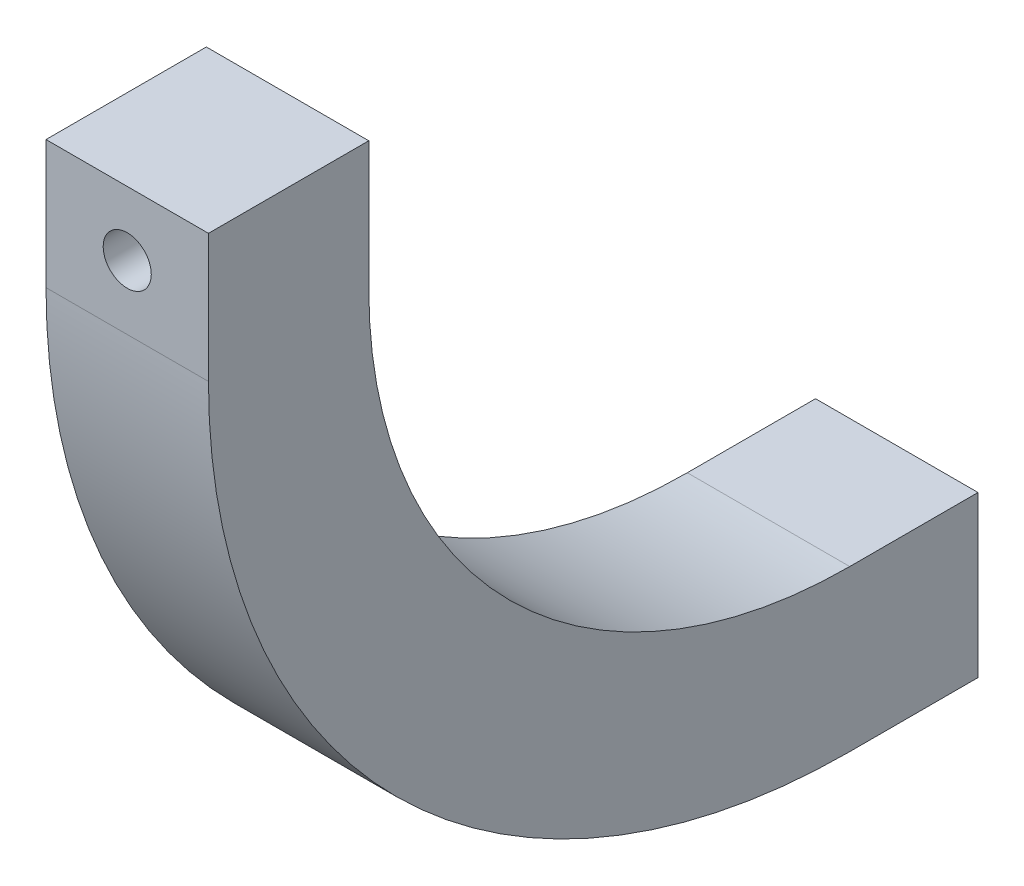
SolidWorks part; units mm, degrees
ref_plane "Front Plane" through (0, 0, 0) normal (0, 0, 1) x (1, 0, 0)
ref_plane "Top Plane" through (0, 0, 0) normal (0, 1, 0) x (1, 0, 0)
ref_plane "Right Plane" through (0, 0, 0) normal (1, 0, 0) x (0, 0, -1)
ref_axis "Z" through (0, 0, 22.75) along (0, 0, -1)
sketch "Sketch4" plane through (0, 0, 0) normal (0, 0, 1) x (1, 0, 0)
  circle A0 centre (0, 0) radius 50 construction
  dimension "D1" = 100
sketch "Sketch5" plane through (0, 0, 0) normal (1, 0, 0) x (0, 0, -1)
  line L0 (-51, 6) -> (-51, 0)
  line L1 (-51, 0) -> (-51, -6)
  line L2 (-66, -6) -> (-66, 6)
  line L6 (-66, 6) -> (-51, 6)
  line L12 (-22.75, 0) -> (-13.0351, 0) construction
  line L13 (0, 0) -> (-14.9091, -14.9091) construction
  line L14 (0, 0) -> (7.0065, 0) construction
  line L15 (0, -51) -> (-6, -51)
  line L16 (6, -51) -> (0, -51)
  line L17 (-6, -66) -> (6, -66)
  line L18 (6, -66) -> (6, -51)
  circle A0 centre (0, 0) radius 14 construction
  arc A1 (-51, -6) -> (-6, -51) centre (-6, -6) ccw
  arc A2 (-66, -6) -> (-6, -66) centre (-6, -6) ccw
  point P2 (9.4307, -21)
  point P4 (0, -2.1363)
  dimension "D1" = 28
  dimension "D4" = 6
  dimension "D2" = 45
  dimension "D3" = 15
  dimension "D5" = 51
sketch "Sketch6" plane through (0, 0, 0) normal (0, 1, 0) x (1, 0, 0)
  circle A0 centre (0, 0) radius 50 construction
  dimension "D1" = 100
extrude "Boss-Extrude1" add sketch "Sketch5" along normal blind 7.6 and the other way blind 7.6
sketch "Sketch7" plane through (0, 0, 0) normal (0, 0, 1) x (1, 0, 0)
  circle A0 centre (0, 0) radius 2.25
  dimension "D1" = 4.5
extrude "Cut-Extrude1" cut sketch "Sketch7" along normal through all
ref_axis "Y" through (0, -9.3489, 0) along (0, -1, 0)
sketch "Sketch16" plane through (0, 0, 0) normal (1, 0, 0) x (0, 0, -1)
  line L0 (0, -67) -> (0, 0) construction
  dimension "D1" = 67
ref_plane "Plane1" through (0, -67, 0) normal (0, 1, 0) x (1, 0, 0)
ref_axis "CX" through (0, -67, 4.4) along (0, 0, -1)
ref_plane "Plane2" through (0, 0, 0) normal (0, 0, -1) x (0, 1, 0)
ref_plane "Plane3" through (0, 0, 0) normal (1, 0, 0) x (0, 0, -1)
ref_axis "CZ" through (0, -8.7018, 0) along (0, -1, 0)
ref_axis "CY" through (-0.6471, -67, 0) along (1, 0, 0)
ref_point "CO"
sketch "Sketch15" plane through (0, -66, 0) normal (0, -1, 0) x (1, 0, 0)
  circle A0 centre (0, 0) radius 1.5
  dimension "D1" = 3
extrude "Cut-Extrude11" cut sketch "Sketch15" against normal blind 6
equation "\"rbracket-width\"= \"L2Thickness\" + 0.2"
equation "\"EyeCaptureRadius\"= ( \"EyeDiameter\" + \"EyeClearance\" ) / 2"
equation "\"rbracket_planetocenterline_dist\"= \"BasePlaneDistance\""
equation "\"EyeDiameter\" = 100"
equation "\"BasePlaneDistance\" = \"EyeDiameter\"/2+\"L2Thickness\"+\"EyeClearance\""
equation "\"EyeClearance\" = 2"
equation "\"D1@Sketch4\"=\"EyeDiameter\""
equation "\"D1@Sketch6\"=\"EyeDiameter\""
equation "\"D1@Boss-Extrude1\"=\"rbracket-width\"/2"
equation "\"D2@Boss-Extrude1\"=\"rbracket-width\"/2"
equation "\"L2Thickness\" = 15"
equation "\"D3@Sketch5\"=\"L2Thickness\""
equation "\"D5@Sketch5\"=(\"EyeDiameter\"+\"EyeClearance\")/2"
equation "\"BearingThickness\"= 6"
equation "\"BearingOD\"=4.5"
equation "\"OuterBearingProudDistance\"= 0"
equation "\"FlangeOD\"=7.5"
equation "\"FlangeThickness\"= 0.75"
equation "\"PrinterFilamentThickness\"= 0.1'For setting distances for things like pressfits"
equation "\"ApplyPrinterOffset\"= 1'Set to 0 for line-to-line. Set to 1 for applying guestimate dimensions to make the printer produce good parts"
equation "\"D1@Cut-Extrude11\"=3*1.5"
equation "\"D1@Sketch16\"=\"BasePlaneDistance\""
